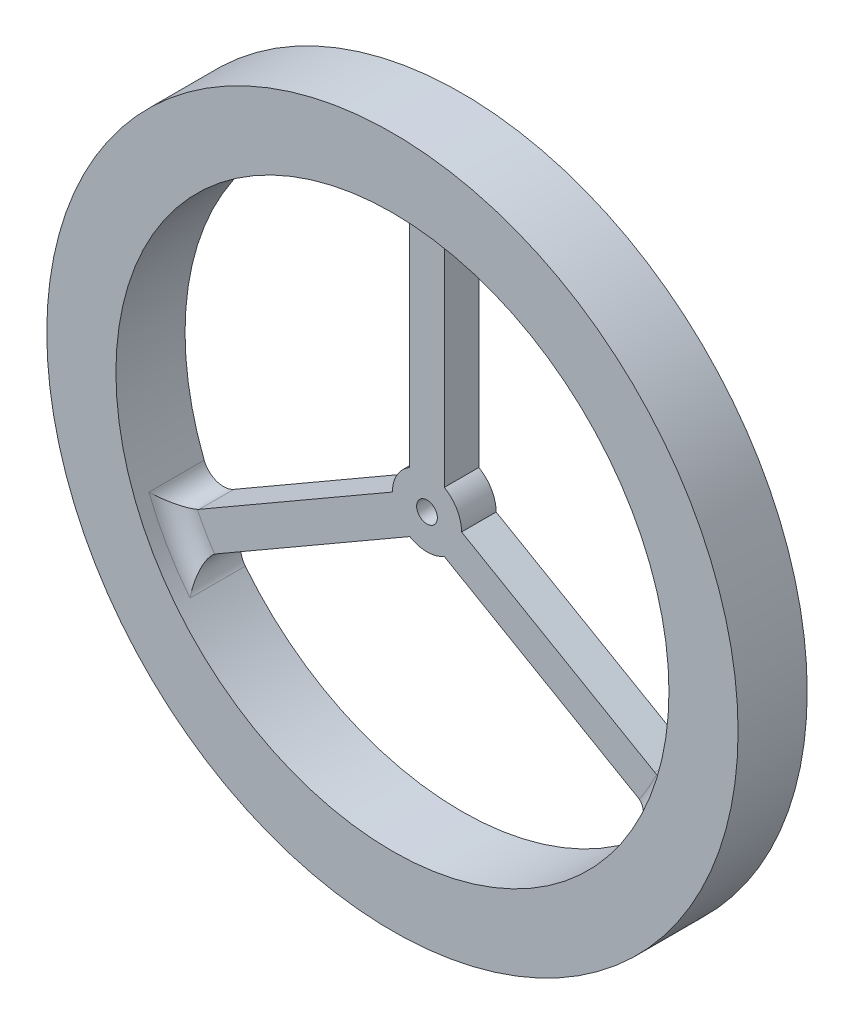
SolidWorks part; units mm, degrees
ref_plane "Front Plane" through (0, 0, 0) normal (0, 0, 1) x (1, 0, 0)
ref_plane "Top Plane" through (0, 0, 0) normal (0, 1, 0) x (1, 0, 0)
ref_plane "Right Plane" through (0, 0, 0) normal (1, 0, 0) x (0, 0, -1)
sketch "Sketch1" plane through (0, 0, 0) normal (0, 0, 1) x (1, 0, 0)
  circle A0 centre (0, 0) radius 50
  circle A1 centre (0, 0) radius 40
  dimension "D1" = 100
  dimension "D2" = 80
extrude "Boss-Extrude1" add sketch "Sketch1" along normal blind 10
sketch "Sketch2" plane through (0, 0, 0) normal (0, 0, 1) x (1, 0, 0)
  line L0 (0, 0) -> (0, 40) construction
  line L2 (-2.5, 40) -> (2.5, 40)
  line L3 (-2.5, 40) -> (-2.5, 0)
  line L4 (-2.5, 0) -> (2.5, 0)
  line L5 (2.5, 40) -> (2.5, 0)
  line L6 (-2.5, 40) -> (2.5, 0) construction
  line L7 (-2.5, 0) -> (2.5, 40) construction
  circle A0 centre (0, 0) radius 40 construction
  point P6 (0, 20)
  dimension "D1" = 5
extrude "Boss-Extrude2" add sketch "Sketch2" along normal blind 5
fillet "Fillet1" radius 3 3 edges at (0, 40, 5) (-2.5, 39.9218, 2.5) (2.5, 39.9218, 2.5)
sketch "Sketch3" plane through (0, 0, 0) normal (1, 0, 0) x (0, 0, -1)
  line L0 (0, 0) -> (12.3064, 0) construction
pattern_circular "CirPattern1" count 3 over 360 about axis through (0, 0, 0) along (0, 0, -1) of "Boss-Extrude2", "Fillet1"
sketch "Sketch5" plane through (0, 0, 0) normal (0, 0, 1) x (1, 0, 0)
  circle A0 centre (0, 0) radius 5
  dimension "D1" = 10
extrude "Boss-Extrude3" add sketch "Sketch5" along normal blind 5
sketch "Sketch7" plane through (0, 0, 5) normal (0, 0, 1) x (1, 0, 0)
  circle A0 centre (0, 0) radius 1.5
  dimension "D1" = 3
extrude "Cut-Extrude1" cut sketch "Sketch7" against normal through all
